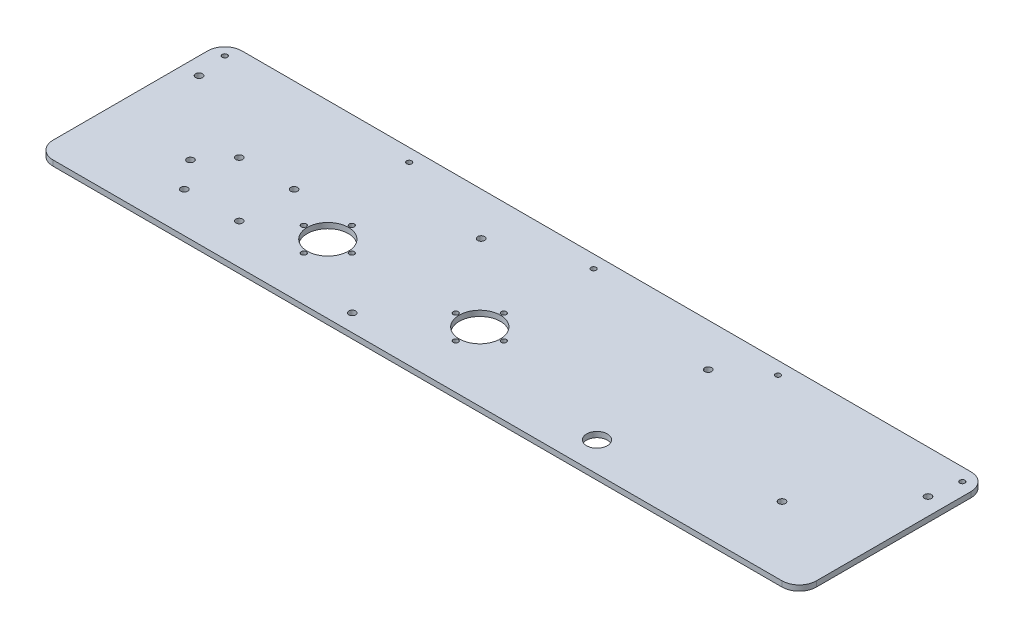
SolidWorks part; units mm, degrees
ref_plane "Front" through (0, 0, 0) normal (0, 0, 1) x (1, 0, 0)
ref_plane "Top" through (0, 0, 0) normal (0, 1, 0) x (1, 0, 0)
ref_plane "Right" through (0, 0, 0) normal (1, 0, 0) x (0, 0, -1)
sketch "Sketch1" plane through (0, 0, 0) normal (0, 1, 0) x (1, 0, 0)
  line L0 (-26.7996, 0) -> (-26.7996, 40)
  line L1 (-26.7996, 0) -> (417.7004, 0)
  line L2 (-26.7996, 0) -> (-26.7996, 110)
  line L3 (-26.7996, 110) -> (417.7004, 110)
  line L4 (417.7004, 0) -> (417.7004, 110)
  line L5 (-26.7996, 40) -> (23.2004, 40)
  line L6 (417.7004, 0) -> (417.7004, 40)
  line L7 (417.7004, 40) -> (367.7004, 40)
  line L8 (23.2004, 40) -> (103.2004, 40)
  line L9 (367.7004, 40) -> (191.7004, 40)
  line L10 (-26.7996, 110) -> (-26.7996, 85)
  line L11 (-26.7996, 85) -> (417.7004, 85)
  line L12 (-26.7996, 85) -> (-16.7996, 85)
  line L13 (417.7004, 85) -> (407.7004, 85)
  line L14 (103.2004, 40) -> (191.7004, 40)
  line L15 (147.4504, 40) -> (147.4504, 85)
  line L16 (279.7004, 40) -> (279.7004, 85)
  line L17 (147.4504, 40) -> (147.4504, 10)
  line L18 (-26.7996, 110) -> (-26.7996, 102.5)
  line L19 (-26.7996, 102.5) -> (417.7004, 102.5)
  line L20 (-26.7996, 102.5) -> (-19.2996, 102.5)
  line L21 (417.7004, 102.5) -> (410.2004, 102.5)
  line L22 (195.4504, 102.5) -> (410.2004, 102.5)
  line L23 (-19.2996, 102.5) -> (195.4504, 102.5)
  line L24 (417.7004, 0) -> (417.7004, 17.2282)
  line L25 (417.7004, 17.2282) -> (282.7004, 17.2282)
  circle A10 centre (367.7004, 40) radius 2
  circle A11 centre (23.2004, 40) radius 2
  circle A12 centre (103.2004, 40) radius 12
  circle A13 centre (103.2004, 40) radius 14
  circle A15 centre (103.2004, 54) radius 1.5
  circle A16 centre (89.2004, 40) radius 1.5
  circle A17 centre (103.2004, 26) radius 1.5
  circle A18 centre (117.2004, 40) radius 1.5
  circle A19 centre (191.7004, 40) radius 12
  circle A20 centre (191.7004, 40) radius 14
  circle A21 centre (191.7004, 26) radius 1.5
  circle A22 centre (205.7004, 40) radius 1.5
  circle A23 centre (191.7004, 54) radius 1.5
  circle A24 centre (177.7004, 40) radius 1.5
  circle A25 centre (-16.7996, 85) radius 2
  circle A26 centre (407.7004, 85) radius 2
  circle A27 centre (147.4504, 85) radius 2
  circle A28 centre (279.7004, 85) radius 2
  circle A29 centre (147.4504, 10) radius 2
  circle A30 centre (195.4504, 102.5) radius 1.5
  circle A31 centre (-19.2996, 102.5) radius 1.5
  circle A32 centre (410.2004, 102.5) radius 1.5
  circle A33 centre (302.8254, 102.5) radius 1.5
  circle A34 centre (88.0754, 102.5) radius 1.5
  circle A35 centre (282.7004, 17.2282) radius 6
  dimension "D3" = 40
  dimension "D7" = 80
  dimension "D8" = 176
  dimension "D9" = 25
  dimension "D11" = 10
  dimension "D12" = 30
  dimension "D13" = 7.5
  dimension "D14" = 7.5
  dimension "D16" = 17.2282
  dimension "D1" = 110
  dimension "D2" = 444.5
  dimension "D4" = 50
  dimension "D5" = 40
  dimension "D6" = 50
  dimension "D10" = 10
  dimension "D15" = 7.5
  dimension "D17" = 135
extrude "Boss-Extrude1" add sketch "Sketch1" along normal blind 3.175 contours A18 L14 A12 L8 A16 A13 A17 | A18 A13 A15 A16 L8 A12 L14 | A24 L14 A19 L9 A22 A20 A23 | A24 A20 A21 A22 L9 A19 L14 | A29 L14 A18 A13 A17 A16 L8 A11 L5 L0 L1 L4 L7 A10 L9 A22 A20 A21 A24 | A28 L11 A27 L15 L14 A24 A20 A23 A22 L9 L16 | A27 L11 A25 L2 L5 A11 L8 A16 A13 A15 A18 L14 L15 | A28 L11 A26 L13 L4 L3 L2 A25 A27 | A28 L16 L9 A10 L7 L4 L13 A26 L11 | A34 L23 A30 L22 A33 A32 L21 L4 L3 L10 L19 A31 region at (196.684, 0, -19.4923) region at (58.5861, 0, -63.184) region at (195.421, 0, -93.7571) region at (195.4504, 0, -106.2666) region at (348.6559, 0, -62.489) region at (93.521, 0, -49.6794) region at (90.515, 0, -38.754) region at (214.7998, 0, -63.4004) region at (204.3858, 0, -41.246) region at (201.3798, 0, -30.3206)
fillet "Fillet1" radius 10 4 edges at (417.7004, 1.5875, -110) (417.7004, 1.5875, 0) (-26.7996, 1.5875, 0) (-26.7996, 1.5875, -110)
sketch "Sketch2" plane through (0, 3.175, 0) normal (0, 1, 0) x (1, 0, 0)
  line L0 (-26.7996, 55.4056) -> (36.2004, 55.4056)
  line L1 (-26.7996, 10) -> (-26.7996, 100) construction
  line L2 (36.2004, 55.4056) -> (68.2004, 55.4056)
  line L3 (-16.7996, 110) -> (407.7004, 110) construction
  line L4 (36.2004, 55.4056) -> (36.2004, 23.4056)
  line L5 (36.2004, 23.4056) -> (68.2004, 23.4056)
  circle A0 centre (36.2004, 55.4056) radius 2
  circle A1 centre (68.2004, 55.4056) radius 2
  circle A2 centre (36.2004, 23.4056) radius 2
  circle A3 centre (68.2004, 23.4056) radius 2
  dimension "D1" = 63
  dimension "D2" = 32
  dimension "D3" = 54.5944
  dimension "D4" = 32
extrude "Cut-Extrude1" cut sketch "Sketch2" against normal blind 10 contours A1 | L4 A0 L2 | L2 A0 L0 | L0 A0 L4 | A3 | A2 region at (36.2004, 3.175, -56.2544) region at (68.2004, 3.175, -57.349) region at (68.2004, 3.175, -25.349) region at (35.3516, 3.175, -54.5568) region at (37.0492, 3.175, -54.5568)
